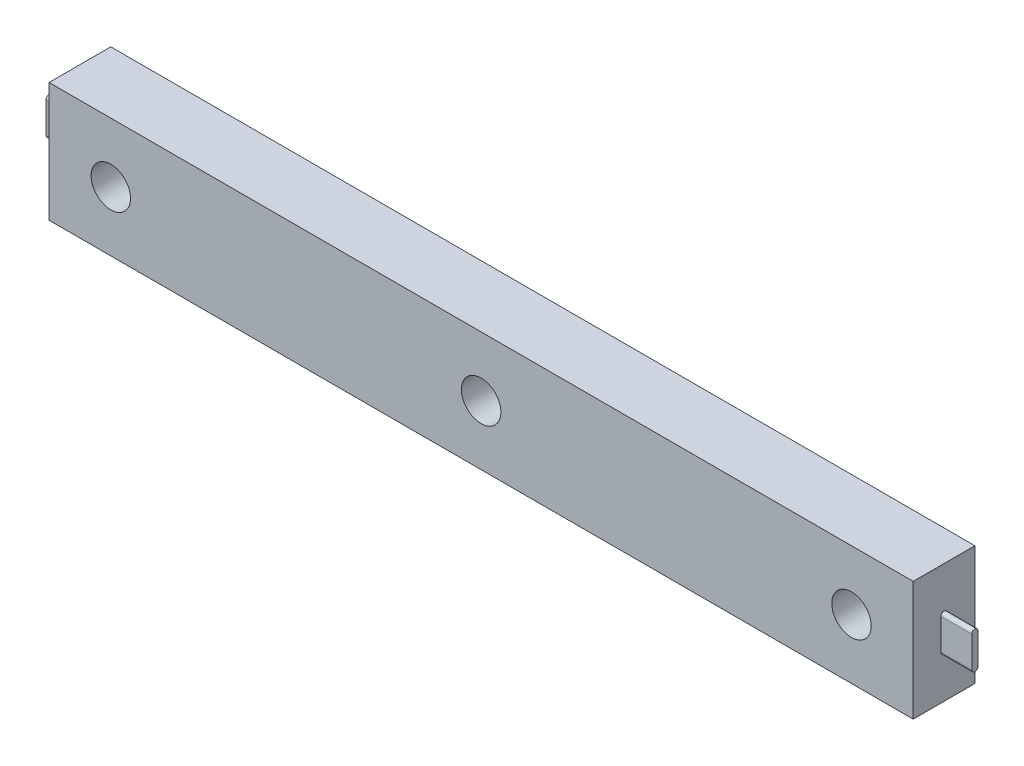
SolidWorks part; units mm, degrees
ref_plane "Front Plane" through (0, 0, 0) normal (0, 0, 1) x (1, 0, 0)
ref_plane "Top Plane" through (0, 0, 0) normal (0, 1, 0) x (1, 0, 0)
ref_plane "Right Plane" through (0, 0, 0) normal (1, 0, 0) x (0, 0, -1)
sketch "Sketch1" plane through (0, 0, 0) normal (0, 0, 1) x (1, 0, 0)
  line L1 (-88.9, -12.2777) -> (88.9, -12.2777)
  line L2 (-88.9, -12.2777) -> (-88.9, 12.2777)
  line L3 (-88.9, 12.2777) -> (88.9, 12.2777)
  line L4 (88.9, -12.2777) -> (88.9, 12.2777)
  line L5 (-88.9, -12.2777) -> (88.9, 12.2777) construction
  line L6 (-88.9, 12.2777) -> (88.9, -12.2777) construction
  circle A0 centre (0, 0) radius 4.064
  circle A1 centre (-76.2, 0) radius 4.064
  circle A2 centre (76.2, 0) radius 4.064
  point P0 (0, 0)
  dimension "D1" = 8.128
  dimension "D2" = 8.128
  dimension "D3" = 8.128
  dimension "D4" = 76.2
  dimension "D5" = 76.2
  dimension "D6" = 177.8
extrude "Boss-Extrude1" add sketch "Sketch1" along normal blind 12.7 contours L2 L1 L4 L3 | A1 | A0 | A2
sketch "Sketch2" plane through (-88.9, 0, 0) normal (-1, 0, 0) x (0, 0, 1)
  line L3 (5.715, -3.175) -> (5.715, 3.175)
  line L4 (6.985, 3.175) -> (6.985, -3.175)
  arc A1 (6.985, 3.175) -> (5.715, 3.175) centre (6.35, 3.175) ccw
  arc A2 (5.715, -3.175) -> (6.985, -3.175) centre (6.35, -3.175) ccw
  dimension "D2" = 1.27
  dimension "D3" = 1.27
extrude "Boss-Extrude2" add sketch "Sketch2" along normal blind 6.35
sketch "Sketch3" plane through (88.9, 0, 0) normal (1, 0, 0) x (0, 0, -1)
  line L0 (-5.715, 3.175) -> (-5.715, -3.175)
  line L1 (-6.985, -3.175) -> (-6.985, 3.175)
  arc A0 (-5.715, 3.175) -> (-6.985, 3.175) centre (-6.35, 3.175) ccw
  arc A1 (-6.985, -3.175) -> (-5.715, -3.175) centre (-6.35, -3.175) ccw
  dimension "D1" = 1.27
  dimension "D2" = 1.27
extrude "Boss-Extrude3" add sketch "Sketch3" along normal blind 6.35
